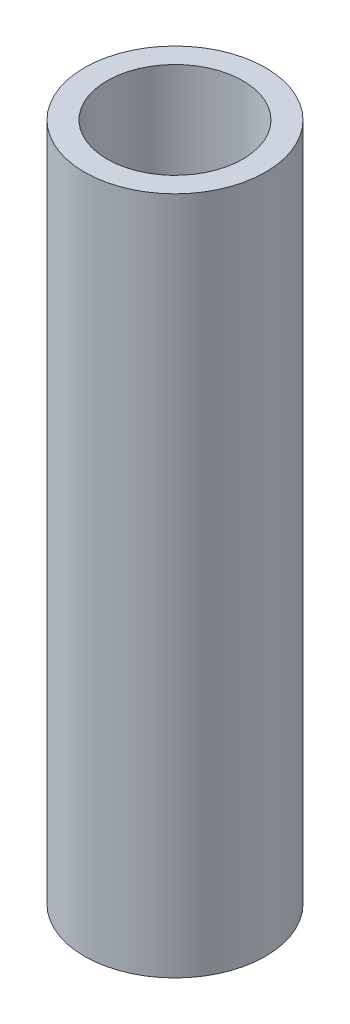
SolidWorks part; units mm, degrees
ref_plane "Front Plane" through (0, 0, 0) normal (0, 0, 1) x (1, 0, 0)
ref_plane "Top Plane" through (0, 0, 0) normal (0, 1, 0) x (1, 0, 0)
ref_plane "Right Plane" through (0, 0, 0) normal (1, 0, 0) x (0, 0, -1)
sketch "Sketch1" plane through (0, 0, 0) normal (0, 1, 0) x (1, 0, 0)
  circle A0 centre (-11.3955, 5.6551) radius 12.7
  circle A1 centre (-11.3955, 5.6551) radius 9.525
extrude "Boss-Extrude1" add sketch "Sketch1" along normal blind 95.25
